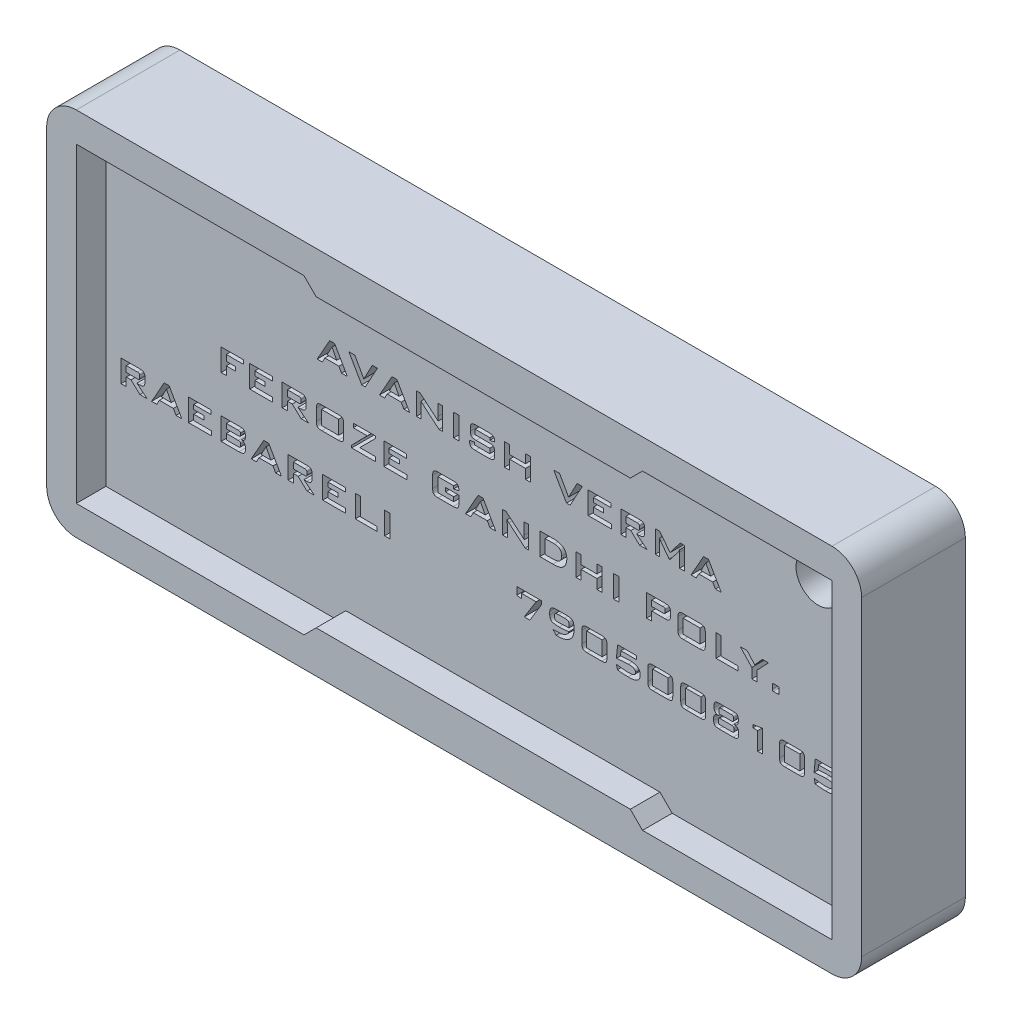
SolidWorks part; units mm, degrees
ref_plane "Front Plane" through (0, 0, 0) normal (0, 0, 1) x (1, 0, 0)
ref_plane "Top Plane" through (0, 0, 0) normal (0, 1, 0) x (1, 0, 0)
ref_plane "Right Plane" through (0, 0, 0) normal (1, 0, 0) x (0, 0, -1)
sketch "Sketch1" plane through (0, 0, 0) normal (0, 0, 1) x (1, 0, 0)
  line L1 (-25.5, -12.5) -> (25.5, -12.5)
  line L2 (-27.5, -10.5) -> (-27.5, 10.5)
  line L3 (-25.5, 12.5) -> (25.5, 12.5)
  line L4 (27.5, -10.5) -> (27.5, 10.5)
  line L5 (-27.5, -12.5) -> (27.5, 12.5) construction
  line L6 (-27.5, 12.5) -> (27.5, -12.5) construction
  arc A0 (-25.5, -12.5) -> (-27.5, -10.5) centre (-25.5, -10.5) cw
  arc A1 (27.5, -10.5) -> (25.5, -12.5) centre (25.5, -10.5) cw
  arc A2 (27.5, 10.5) -> (25.5, 12.5) centre (25.5, 10.5) ccw
  arc A3 (-25.5, 12.5) -> (-27.5, 10.5) centre (-25.5, 10.5) ccw
  point P0 (0, 0)
  dimension "D3" = 2
  dimension "D1" = 55
  dimension "D2" = 25
extrude "Boss-Extrude1" add sketch "Sketch1" along normal blind 7
sketch "Sketch2" plane through (0, 0, 0) normal (0, 0, -1) x (-1, 0, 0)
  line L0 (-27.5, -10.5) -> (-27.5, 10.5) construction
  line L1 (-25.5, -10.5) -> (-11.552, -10.5)
  line L2 (-25.5, -10.5) -> (-25.5, 10.5)
  line L3 (-25.5, 10.5) -> (-11.552, 10.5)
  line L4 (25.5, -10.5) -> (25.5, 10.5)
  line L5 (-25.5, -10.5) -> (-23.5, -9.6765) construction
  line L6 (-25.5, 10.5) -> (-23.5, 9.6765) construction
  line L7 (-25.5, 12.5) -> (25.5, 12.5) construction
  line L8 (-11.552, 10.5) -> (-10.7284, 9.6765)
  line L13 (-23.5, -9.6765) -> (0, 0) construction
  line L14 (10.0955, 10.5) -> (25.5, 10.5)
  line L15 (-11.552, 10.5) -> (-25.5, 10.5)
  line L16 (9.272, 9.6765) -> (10.0955, 10.5)
  line L17 (-11.552, -10.5) -> (-10.7284, -9.6765)
  line L18 (10.0955, -10.5) -> (25.5, -10.5)
  line L19 (9.272, -9.6765) -> (10.0955, -10.5)
  line L20 (-11.552, -10.5) -> (-25.5, -10.5)
  line L22 (10.0955, -10.5) -> (9.272, -9.6765)
  line L23 (25.5, -10.5) -> (10.0955, -10.5)
  line L24 (25.5, -10.5) -> (25.5, 10.5)
  line L25 (25.5, 10.5) -> (10.0955, 10.5)
  line L26 (-25.5, -10.5) -> (-25.5, 10.5)
  line L27 (23.5, -9.6765) -> (-25.5, 10.5) construction
  line L28 (25.5, 10.5) -> (-25.5, -10.5) construction
  line L29 (9.272, -9.6765) -> (-10.7284, -9.6765)
  line L31 (9.272, 9.6765) -> (-10.7284, 9.6765)
  line L33 (23.5, -9.6765) -> (-23.5, 9.6765) construction
  line L34 (23.5, 9.6765) -> (-23.5, -9.6765) construction
  line L35 (-10.7284, -9.6765) -> (-11.552, -10.5)
  line L36 (10.0955, 10.5) -> (9.272, 9.6765)
  line L37 (-10.7284, 9.6765) -> (-11.552, 10.5)
  point P0 (0, 0)
  point P10 (0, 0)
  dimension "D1" = 2
  dimension "D2" = 2
extrude "Cut-Extrude1" cut sketch "Sketch2" against normal blind 2 contours L16 L31 L8 L3 L2 L1 L17 L29 L19 L18 L4 L14 region at (-0.0241, 0, 0)
sketch "Sketch3" plane through (0, 0, 7) normal (0, 0, 1) x (1, 0, 0)
  line L0 (-27.5, 10.5) -> (-27.5, -10.5) construction
  line L1 (-25.5, -10.5) -> (-10.1359, -10.5)
  line L2 (-25.5, -10.5) -> (-25.5, 10.5)
  line L3 (-25.5, 10.5) -> (-10.1359, 10.5)
  line L4 (25.5, -10.5) -> (25.5, 10.5)
  line L5 (-25.5, -10.5) -> (-23.5, -9.6765) construction
  line L6 (-25.5, 10.5) -> (-23.5, 9.6765) construction
  line L7 (25.5, 12.5) -> (-25.5, 12.5) construction
  line L8 (-10.1359, 10.5) -> (-9.3123, 9.6765)
  line L9 (-9.3123, -9.6765) -> (11.8893, -9.6765)
  line L13 (-23.5, -9.6765) -> (0, 0) construction
  line L14 (-23.5, 9.6765) -> (0, 0) construction
  line L17 (12.7129, 10.5) -> (11.8893, 9.6765)
  line L18 (12.7129, 10.5) -> (25.5, 10.5)
  line L19 (-10.1359, -10.5) -> (-9.3123, -9.6765)
  line L20 (-9.3123, -9.6765) -> (11.8893, -9.6765)
  line L21 (11.8893, -9.6765) -> (12.7129, -10.5)
  line L22 (-9.3123, 9.6765) -> (11.8893, 9.6765)
  line L23 (0, 0) -> (25.5, -10.5) construction
  line L24 (0, 0) -> (25.5, 10.5) construction
  line L25 (12.7129, -10.5) -> (25.5, -10.5)
  point P0 (0, 0)
  point P10 (0, 0)
  dimension "D1" = 2
  dimension "D2" = 2
extrude "Cut-Extrude2" cut sketch "Sketch3" against normal blind 2 contours L21 L25 L4 L18 L17 L22 L8 L3 L2 L1 L19 L9 region at (-0.0452, 0, 7)
sketch "Sketch4" plane through (0, 0, 5) normal (0, 0, 1) x (1, 0, 0)
  text T0 "            AVANISH VERMA\r\n      FEROZE GANDHI POLY.\r\nRAEBARELI       7905008105" font "BankGothic Md BT" height 1.5
extrude "Cut-Extrude10" cut sketch "Sketch4" against normal blind 3
sketch "Sketch5" plane through (0, 0, 5) normal (0, 0, 1) x (1, 0, 0)
  circle A0 centre (22.5719, 8.0869) radius 1.5
extrude "Cut-Extrude11" cut sketch "Sketch5" against normal blind 3
